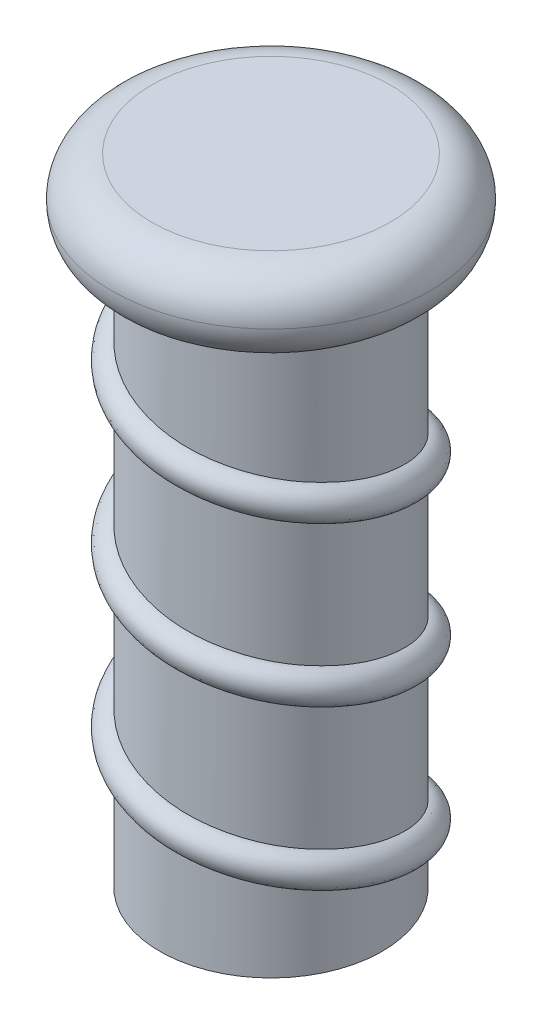
SolidWorks part; units mm, degrees
ref_plane "Front Plane" through (0, 0, 0) normal (0, 0, 1) x (1, 0, 0)
ref_plane "Top Plane" through (0, 0, 0) normal (0, 1, 0) x (1, 0, 0)
ref_plane "Right Plane" through (0, 0, 0) normal (1, 0, 0) x (0, 0, -1)
sketch "Sketch1" plane through (0, 0, 0) normal (0, 1, 0) x (1, 0, 0)
  circle A0 centre (0, 0) radius 1.4
  dimension "D1" = 2.8
extrude "Boss-Extrude1" add sketch "Sketch1" along normal blind 7
sketch "Sketch2" plane through (0, 7, 0) normal (0, 1, 0) x (1, 0, 0)
  circle A0 centre (0, 0) radius 2
  dimension "D1" = 4
extrude "Boss-Extrude2" add sketch "Sketch2" along normal blind 1
fillet "Fillet3" radius 0.5 2 edges at (0, 7, 2) (0, 8, 2)
sketch "Sketch3" plane through (0, 0, 0) normal (0, 1, 0) x (1, 0, 0)
  circle A0 centre (0, 0) radius 1.4 construction
  circle A1 centre (0, 0) radius 1.4
curve "Helix/Spiral1" pitch 2 height 6.5 radius 1.4 left hand yes centre (0, 0, 0) axis (0, 1, 0) start towards (0, 0, 1)
sweep "Sweep1" add path "Helix/Spiral1" circular profile diameter 0.4 parameters "D3"=0.4
